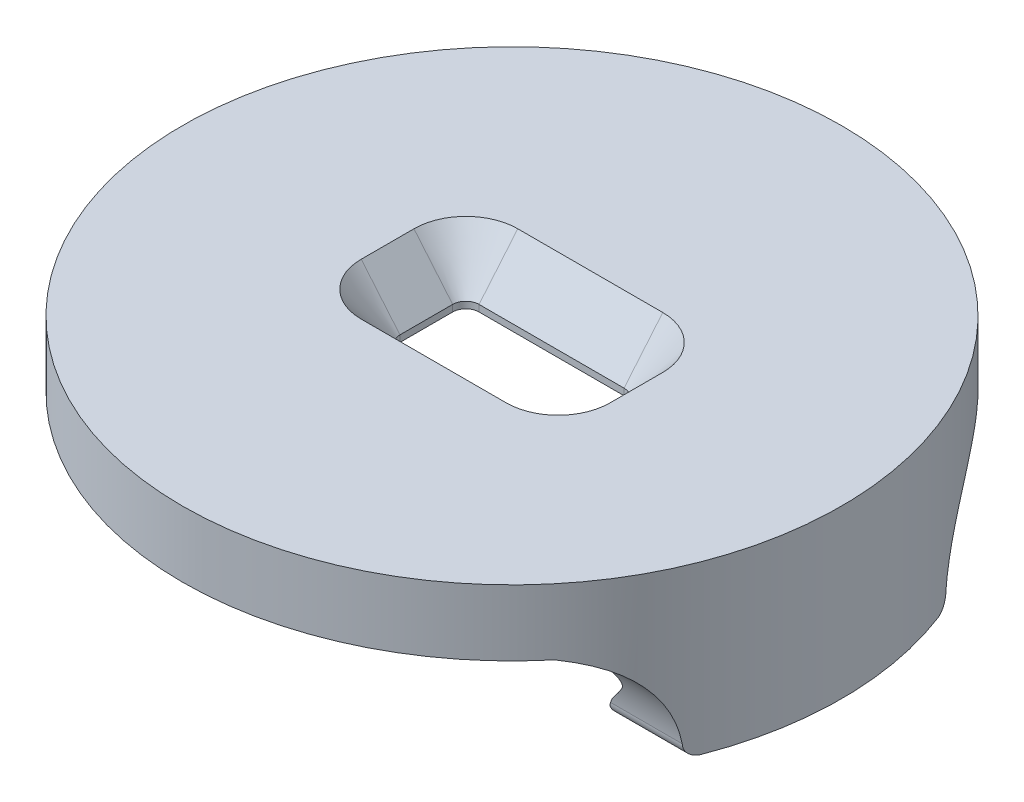
SolidWorks part; units mm, degrees
ref_plane "Front Plane" through (0, 0, 0) normal (0, 0, 1) x (1, 0, 0)
ref_plane "Top Plane" through (0, 0, 0) normal (0, 1, 0) x (1, 0, 0)
ref_plane "Right Plane" through (0, 0, 0) normal (1, 0, 0) x (0, 0, -1)
sketch "Sketch1" plane through (0, 0, 0) normal (0, 1, 0) x (1, 0, 0)
  circle A0 centre (0, 0) radius 25
  dimension "D1" = 50
extrude "Boss-Extrude1" add sketch "Sketch1" along normal blind 5
sketch "Sketch2" plane through (0, 0, 0) normal (0, -1, 0) x (1, 0, 0)
  line L1 (11, -10) -> (-11, -10)
  line L2 (11, -10) -> (11, 10)
  line L3 (11, 10) -> (-11, 10)
  line L4 (-11, -10) -> (-11, 10)
  line L5 (11, -10) -> (-11, 10) construction
  line L6 (11, 10) -> (-11, -10) construction
  line L7 (5, -10) -> (-5, -10)
  line L8 (5, -10) -> (5, -14)
  line L9 (5, -14) -> (-5, -14)
  line L10 (-5, -10) -> (-5, -14)
  line L11 (5, -10) -> (-5, -14) construction
  line L12 (5, -14) -> (-5, -10) construction
  point P0 (0, 0)
  point P10 (0, -12)
  point P11 (0, -10)
  dimension "D1" = 22
  dimension "D2" = 20
  dimension "D3" = 10
  dimension "D4" = 4
extrude "Cut-Extrude1" cut sketch "Sketch2" against normal blind 1 contours L4 L1 L2 L3 | L1 L10 L9 L8
fillet "Fillet1" radius 3 4 edges at (11, 0.5, 10) (11, 0.5, -10) (-11, 0.5, -10) (-11, 0.5, 10)
sketch "Sketch3" plane through (0, 1, 0) normal (0, -1, 0) x (1, 0, 0)
  line L0 (0, 0) -> (0, 6.6) construction
  line L1 (7.6, 6.6) -> (-7.6, 6.6) construction
  line L4 (11, -7) -> (11, 7) construction
  line L5 (8, 10) -> (-8, 10) construction
  circle A1 centre (-7.6, 6.6) radius 1.4
  circle A2 centre (7.6, 6.6) radius 1.4
  point P6 (0, 6.6)
  dimension "D3" = 3.4
  dimension "D1" = 2.8
  dimension "D2" = 3.4
extrude "Cut-Extrude2" cut sketch "Sketch3" against normal blind 3
sketch "Sketch4" plane through (0, 1, 0) normal (0, -1, 0) x (1, 0, 0)
  line L1 (6.5, 3) -> (-6.5, 3)
  line L2 (6.5, 3) -> (6.5, -3)
  line L3 (6.5, -3) -> (-6.5, -3)
  line L4 (-6.5, 3) -> (-6.5, -3)
  line L5 (6.5, 3) -> (-6.5, -3) construction
  line L6 (6.5, -3) -> (-6.5, 3) construction
  point P0 (0, 0)
  dimension "D1" = 6
  dimension "D2" = 13
extrude "Cut-Extrude3" cut sketch "Sketch4" against normal through all
fillet "Fillet2" radius 1 4 edges at (-6.5, 3, 3) (6.5, 3, 3) (-6.5, 3, -3) (6.5, 3, -3)
fillet "Fillet3" radius 1.5 4 edges at (5, 0.5, -10) (5, 0.5, -14) (-5, 0.5, -14) (-5, 0.5, -10)
chamfer "Chamfer1" distance 3.5 angle 40 8 edges at (0, 5, -3) (6.2071, 5, -2.7071) (-6.2071, 5, -2.7071) (6.5, 5, 0) (-6.5, 5, 0) (6.2071, 5, 2.7071) (-6.2071, 5, 2.7071) (0, 5, 3)
sketch "Sketch5" plane through (0, 0, 0) normal (0, -1, 0) x (1, 0, 0)
  circle A0 centre (0, 0) radius 25
  circle A1 centre (0, 0) radius 22
  circle A2 centre (0, 0) radius 25 construction
  dimension "D1" = 3
extrude "Boss-Extrude2" add sketch "Sketch5" along normal blind 10
ref_plane "Plane1" through (0, 0, 0) normal (1, 0, 0) x (0, 0, -1)
sketch "Sketch6" plane through (0, 0, 0) normal (1, 0, 0) x (0, 0, -1)
  line L0 (25, 5) -> (-25, 5) construction
  line L1 (-16, 0) -> (16, 0) construction
  line L3 (-16, 0) -> (-25, 0)
  line L6 (16, 0) -> (25, 0)
  line L7 (0, 5) -> (0, -10) construction
  line L8 (-10, -6.662) -> (-10, -7.662)
  line L9 (-10, -7.662) -> (10, -7.662)
  line L10 (10, -7.662) -> (10, -6.662)
  line L11 (-25, 0) -> (-25, -10)
  line L12 (-25, -10) -> (25, -10)
  line L13 (25, -10) -> (25, 0)
  arc A0 (-16, 0) -> (-10, -6.662) centre (-17.9236, -7.7653) cw
  arc A1 (16, 0) -> (10, -6.662) centre (17.9236, -7.7653) ccw
  point P7 (0, 0)
  dimension "D7" = 8
  dimension "D8" = 8
  dimension "D13" = 10
  dimension "D1" = 5
  dimension "D2" = 32
  dimension "D3" = 9
  dimension "D4" = 9
  dimension "D5" = 10
  dimension "D6" = 10
  dimension "D9" = 1
  dimension "D10" = 1
  dimension "D11" = 20
  dimension "D12" = 7.662
extrude "Cut-Extrude4" cut sketch "Sketch6" against normal through all both and the other way through all
sketch "Sketch7" plane through (0, -7.662, 0) normal (0, -1, 0) x (1, 0, 0)
  line L0 (-22.9129, 10) -> (-17.3205, 10)
  line L1 (-22.9129, -10) -> (-17.3205, -10)
  line L2 (22.9129, -10) -> (17.3205, -10)
  line L3 (22.9129, 10) -> (17.3205, 10)
  line L4 (-22.9129, -10) -> (-19.5959, -10) construction
  line L5 (-22.9129, 10) -> (-19.5959, 10) construction
  line L6 (19.5959, -10) -> (22.9129, -10) construction
  line L7 (19.5959, 10) -> (22.9129, 10) construction
  circle A0 centre (0, 0) radius 25
  circle A1 centre (0, 0) radius 20
  arc A2 (-22.9129, 10) -> (-22.9129, -10) centre (0, 0) ccw construction
  line M1 (-22.9129, -10) -> (-19.5959, -10)
  arc M2 (-19.5959, -10) -> (-19.5959, 10) centre (0, 0) cw
  line M3 (-19.5959, 10) -> (-22.9129, 10)
  arc M4 (-22.9129, 10) -> (-22.9129, -10) centre (0, 0) ccw
  dimension "D1" = 5
  dimension "D2" = 5.5924
extrude "Boss-Extrude3" add sketch "Sketch7" against normal blind 1 contours A1 L0 L1 M2 | M4 M1 M2 M3 | A1 L2 A0 L3
chamfer "Chamfer2" distance 2 angle 50 2 edges at (22, -6.662, 0) (-22, -6.662, 0)
fillet "Fillet5" radius 2 2 edges at (22, -4.2785, 0) (-22, -4.2785, 0)
fillet "Fillet4" radius 1 6 edges at (20.1167, -7.662, 10) (20.1167, -7.662, -10) (-17.1545, 0, -16) (17.1545, 0, -16) (17.1545, 0, 16) (-17.1545, 0, 16)
fillet "Fillet6" radius 2 2 edges at (20, -6.662, 0) (-20, -6.662, 0)
